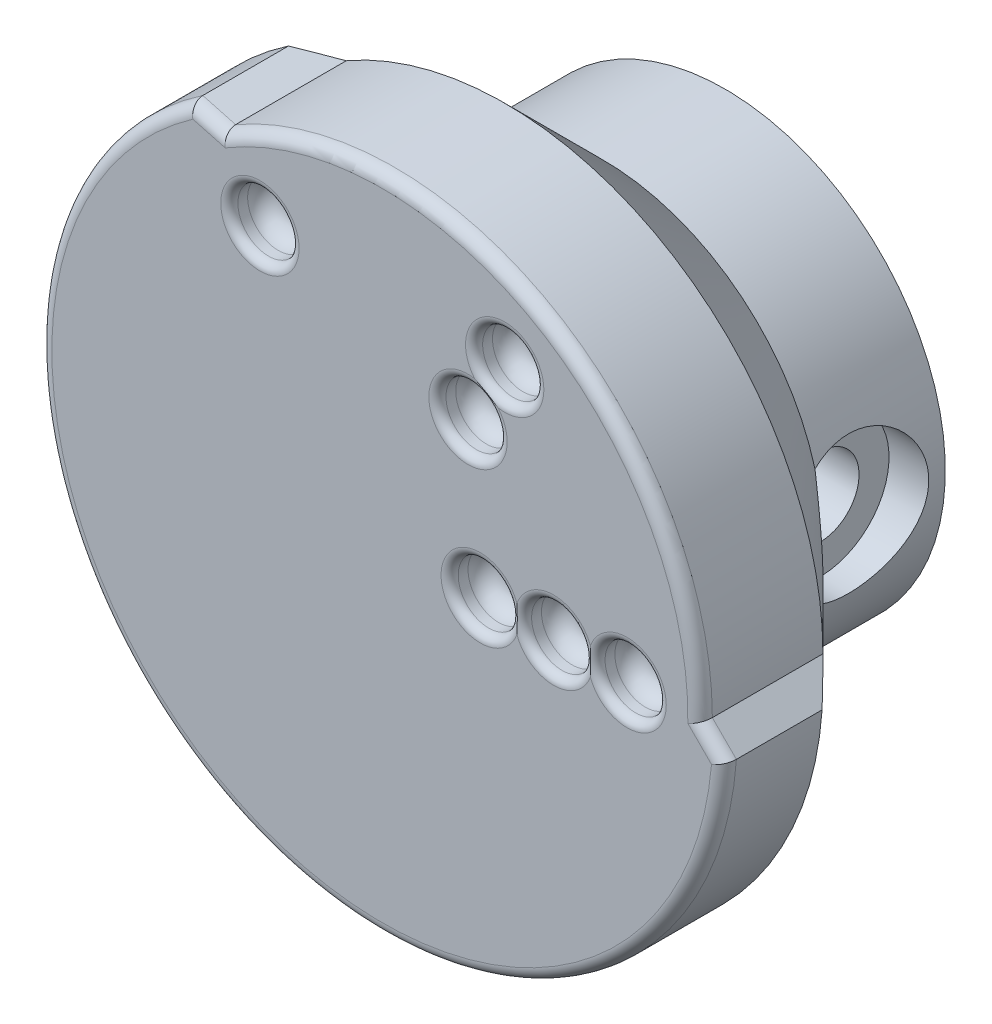
SolidWorks part; units mm, degrees
ref_plane "Front Plane" through (0, 0, 0) normal (0, 0, 1) x (1, 0, 0)
ref_plane "Top Plane" through (0, 0, 0) normal (0, 1, 0) x (1, 0, 0)
ref_plane "Right Plane" through (0, 0, 0) normal (1, 0, 0) x (0, 0, -1)
sketch "Sketch1" plane through (0, 0, 0) normal (0, 0, 1) x (1, 0, 0)
  circle A0 centre (0, 0) radius 32.5
  dimension "D1" = 65
extrude "Boss-Extrude1" add sketch "Sketch1" along normal blind 13.25
sketch "Sketch2" plane through (0, 0, 13.25) normal (0, 0, 1) x (1, 0, 0)
  circle A0 centre (0, 0) radius 25
  dimension "D1" = 50
extrude "Cut-Extrude1" cut sketch "Sketch2" against normal blind 9.25
sketch "Sketch3" plane through (0, 0, 4) normal (0, 0, 1) x (1, 0, 0)
  line L1 (0, 4.7631) -> (-4.125, 2.3816)
  line L2 (-4.125, 2.3816) -> (-4.125, -2.3816)
  line L3 (-4.125, -2.3816) -> (0, -4.7631)
  line L4 (0, -4.7631) -> (4.125, -2.3816)
  line L5 (4.125, -2.3816) -> (4.125, 2.3816)
  line L6 (4.125, 2.3816) -> (0, 4.7631)
  circle A0 centre (0, 0) radius 4.125 construction
  dimension "D1" = 8.25
extrude "Cut-Extrude2" cut sketch "Sketch3" against normal through all
fillet "Fillet1" [suppressed] radius 2
fillet "Inner Fillet" [suppressed] radius 2
sketch "Sketch4" plane through (0, 0, 13.25) normal (0, 0, 1) x (1, 0, 0)
  circle A0 centre (0, 0) radius 29.5
  dimension "D1" = 59
extrude "Cut-Extrude3" cut sketch "Sketch4" against normal blind 3
sketch "Sketch5" plane through (0, 0, 0) normal (0, 0, -1) x (-1, 0, 0)
  line L0 (0, 37.5748) -> (0, -64.9877) construction
sketch "Sketch6" plane through (0, 0, 0) normal (1, 0, 0) x (0, 0, -1)
  line L0 (-13.25, 32.5) -> (-13.25, -32.5) construction
  line L1 (0, -32.5) -> (0, 32.5) construction
  line L2 (-13.25, 32.5) -> (-13.25, -32.5) construction
  line L3 (0, -32.5) -> (0, 32.5) construction
sketch "Sketch7" plane through (0, 0, 0) normal (0, 0, -1) x (-1, 0, 0)
  line L0 (33.5665, -32.5) -> (-65.5928, -32.5) construction
  line L7 (-4.125, 2.3816) -> (-4.125, -2.3816)
  line L8 (0, 4.7631) -> (-4.125, 2.3816)
  line L9 (4.125, 2.3816) -> (0, 4.7631)
  line L10 (4.125, -2.3816) -> (4.125, 2.3816)
  line L11 (0, -4.7631) -> (4.125, -2.3816)
  line L12 (-4.125, -2.3816) -> (0, -4.7631)
  line L13 (-4.125, 2.3816) -> (-4.125, -2.3816)
  line L14 (0, 4.7631) -> (-4.125, 2.3816)
  line L15 (4.125, 2.3816) -> (0, 4.7631)
  line L16 (4.125, -2.3816) -> (4.125, 2.3816)
  line L17 (0, -4.7631) -> (4.125, -2.3816)
  line L18 (-4.125, -2.3816) -> (0, -4.7631)
  circle A0 centre (-23.4554, -36.9311) radius 4 construction
  circle A1 centre (-23.4554, -36.9311) radius 9
  arc A2 (-23.9766, -21.9402) -> (-9.6651, -31.0296) centre (-23.4554, -36.9311) ccw
  circle A3 centre (-23.4554, -36.9311) radius 11.25 construction
  circle A4 centre (0, 0) radius 32.5 construction
  circle A6 centre (0, 0) radius 32.5
  arc A7 (-9.6651, -31.0296) -> (-23.9766, -21.9402) centre (0, 0) ccw
  dimension "D1" = 8
  dimension "D2" = 18
  dimension "D3" = 30
  dimension "D4" = 22.5
  dimension "D5" = 0
  dimension "D6" = 0
extrude "Boss-Extrude2" add sketch "Sketch7" against normal blind 1.5
sketch "Sketch8" plane through (0, 0, 1.5) normal (0, 0, 1) x (1, 0, 0)
  line L0 (23.4554, -36.9311) -> (23.4554, -25.6811) construction
  line L1 (23.4554, -36.9311) -> (33.1982, -42.5561) construction
  line L2 (23.4554, -36.9311) -> (13.7126, -42.5561) construction
  arc A0 (33.3207, -42.3382) -> (23.7054, -25.6839) centre (23.4554, -36.9311) ccw
  arc A1 (9.6651, -31.0296) -> (23.9766, -21.9402) centre (23.4554, -36.9311) ccw construction
  circle A2 centre (23.4554, -36.9311) radius 15
  arc A3 (23.6707, -25.8082) -> (23.2401, -25.8082) centre (23.4554, -36.9311) ccw
  arc A4 (23.2054, -25.6839) -> (23.2401, -25.8082) centre (23.4554, -25.6811) ccw
  arc A5 (9.6651, -31.0296) -> (23.9766, -21.9402) centre (23.4554, -36.9311) ccw
  arc A6 (9.6651, -31.0296) -> (23.9766, -21.9402) centre (0, 0) ccw
  circle A7 centre (23.4554, -36.9311) radius 15
  arc A9 (23.6707, -25.8082) -> (23.7054, -25.6839) centre (23.4554, -25.6811) ccw
  arc A10 (33.3207, -42.3382) -> (33.1957, -42.3061) centre (33.1982, -42.5561) ccw
  arc A11 (32.9805, -42.679) -> (33.0708, -42.7712) centre (33.1982, -42.5561) ccw
  arc A12 (23.2054, -25.6839) -> (13.59, -42.3382) centre (23.4554, -36.9311) ccw
  arc A13 (13.84, -42.7712) -> (13.9303, -42.679) centre (13.7126, -42.5561) ccw
  arc A14 (13.84, -42.7712) -> (33.0708, -42.7712) centre (23.4554, -36.9311) ccw
  arc A15 (13.715, -42.3061) -> (13.59, -42.3382) centre (13.7126, -42.5561) ccw
  arc A16 (13.715, -42.3061) -> (13.9303, -42.679) centre (23.4554, -36.9311) ccw
  arc A17 (32.9805, -42.679) -> (33.1957, -42.3061) centre (23.4554, -36.9311) ccw
  dimension "D1" = 22.5
  dimension "D3" = 22.25
  dimension "D4" = 0.5
  dimension "D7" = 0.5
  dimension "D8" = 0.5
  dimension "D5" = 120
  dimension "D6" = 120
  dimension "D2" = 0
sketch "Sketch9" plane through (0, 0, 1.5) normal (0, 0, 1) x (1, 0, 0)
  circle A0 centre (23.4554, -36.9311) radius 11.125
  arc A1 (9.6651, -31.0296) -> (23.9766, -21.9402) centre (23.4554, -36.9311) ccw construction
  arc A2 (9.6651, -31.0296) -> (23.9766, -21.9402) centre (0, 0) ccw construction
  arc A3 (9.6651, -31.0296) -> (23.9766, -21.9402) centre (23.4554, -36.9311) ccw
  arc A4 (9.6651, -31.0296) -> (23.9766, -21.9402) centre (0, 0) ccw
  dimension "D1" = 22.25
extrude "Boss-Extrude5" add sketch "Sketch9" along normal blind 7.5
sketch "Sketch10" plane through (0, 0, 13.25) normal (0, 0, 1) x (1, 0, 0)
  line L0 (23.4554, -25.5561) -> (23.4554, -36.9311) construction
  line L1 (23.4554, -36.9311) -> (33.3064, -42.6186) construction
  line L2 (23.4554, -36.9311) -> (13.6043, -42.6186) construction
  circle A0 centre (23.4554, -36.9311) radius 11.125 construction
  arc A1 (13.6139, -42.1187) -> (14.0421, -42.8603) centre (23.4554, -36.9311) ccw
  arc A2 (13.8638, -43.046) -> (33.047, -43.046) centre (23.4554, -36.9311) ccw
  arc A3 (23.8835, -25.8144) -> (23.9553, -25.5671) centre (23.4554, -25.5561) ccw
  arc A4 (13.6139, -42.1187) -> (13.3639, -42.1802) centre (13.6043, -42.6186) ccw
  arc A5 (32.8687, -42.8603) -> (33.047, -43.046) centre (33.3064, -42.6186) ccw
  circle A6 centre (23.4554, -36.9311) radius 11.125 construction
  arc A7 (32.8687, -42.8603) -> (33.2968, -42.1187) centre (23.4554, -36.9311) ccw
  arc A8 (13.8638, -43.046) -> (14.0421, -42.8603) centre (13.6043, -42.6186) ccw
  circle A9 centre (23.4554, -36.9311) radius 11.375 construction
  arc A10 (33.5468, -42.1802) -> (33.2968, -42.1187) centre (33.3064, -42.6186) ccw
  arc A11 (33.5468, -42.1802) -> (23.9553, -25.5671) centre (23.4554, -36.9311) ccw
  arc A12 (23.8835, -25.8144) -> (23.0272, -25.8144) centre (23.4554, -36.9311) ccw
  arc A13 (22.9555, -25.5671) -> (23.0272, -25.8144) centre (23.4554, -25.5561) ccw
  arc A14 (22.9555, -25.5671) -> (13.3639, -42.1802) centre (23.4554, -36.9311) ccw
  dimension "D4" = 1
  dimension "D5" = 1
  dimension "D6" = 1
  dimension "D2" = 120
  dimension "D3" = 120
  dimension "D1" = 0.25
extrude "Cut-Extrude4" cut sketch "Sketch10" against normal up to surface (11.75 mm away) up to face at (34.5804, -36.9311, 1.5)
sketch "Sketch11" plane through (0, 0, 9) normal (0, 0, 1) x (1, 0, 0)
  circle A91 centre (23.4554, -36.9311) radius 11.9872
  arc A104 (22.8427, -25.7028) -> (18.685, -26.7481) centre (23.4554, -36.9311) ccw
  arc A105 (22.8427, -25.7028) -> (22.9615, -25.9472) centre (23.4554, -25.5561) ccw
  arc A106 (23.9493, -25.9472) -> (22.9615, -25.9472) centre (23.4554, -36.9311) ccw
  arc A107 (23.9493, -25.9472) -> (24.0681, -25.7028) centre (23.4554, -25.5561) ccw
  arc A108 (33.4857, -42.0147) -> (24.0681, -25.7028) centre (23.4554, -36.9311) ccw
  arc A109 (33.4857, -42.0147) -> (33.2147, -41.9953) centre (33.3064, -42.6186) ccw
  arc A110 (32.7208, -42.8508) -> (33.2147, -41.9953) centre (23.4554, -36.9311) ccw
  arc A111 (32.7208, -42.8508) -> (32.873, -43.0759) centre (33.3064, -42.6186) ccw
  arc A112 (13.6961, -41.9953) -> (13.425, -42.0147) centre (13.6043, -42.6186) ccw
  arc A113 (16.2665, -28.2841) -> (13.425, -42.0147) centre (23.4554, -36.9311) ccw
  arc A114 (14.0377, -43.0759) -> (32.873, -43.0759) centre (23.4554, -36.9311) ccw
  arc A115 (14.0377, -43.0759) -> (14.19, -42.8508) centre (13.6043, -42.6186) ccw
  arc A116 (13.6961, -41.9953) -> (14.19, -42.8508) centre (23.4554, -36.9311) ccw
  arc A117 (22.8427, -25.7028) -> (16.2665, -28.2841) centre (23.4554, -36.9311) ccw
  arc A118 (22.8427, -25.7028) -> (22.9615, -25.9472) centre (23.4554, -25.5561) ccw
  arc A119 (23.9493, -25.9472) -> (22.9615, -25.9472) centre (23.4554, -36.9311) ccw
  arc A120 (23.9493, -25.9472) -> (24.0681, -25.7028) centre (23.4554, -25.5561) ccw
  arc A121 (33.4857, -42.0147) -> (24.0681, -25.7028) centre (23.4554, -36.9311) ccw
  arc A122 (33.4857, -42.0147) -> (33.2147, -41.9953) centre (33.3064, -42.6186) ccw
  arc A123 (32.7208, -42.8508) -> (33.2147, -41.9953) centre (23.4554, -36.9311) ccw
  arc A124 (32.7208, -42.8508) -> (32.873, -43.0759) centre (33.3064, -42.6186) ccw
  arc A125 (13.6961, -41.9953) -> (13.425, -42.0147) centre (13.6043, -42.6186) ccw
  arc A126 (16.2665, -28.2841) -> (13.425, -42.0147) centre (23.4554, -36.9311) ccw
  arc A127 (14.0377, -43.0759) -> (32.873, -43.0759) centre (23.4554, -36.9311) ccw
  arc A128 (14.0377, -43.0759) -> (14.19, -42.8508) centre (13.6043, -42.6186) ccw
  arc A129 (13.6961, -41.9953) -> (14.19, -42.8508) centre (23.4554, -36.9311) ccw
  dimension "D1" = 0.13
extrude "Boss-Extrude6" add sketch "Sketch11" against normal up to surface (7.5 mm away) up to face at (23.4554, -36.9311, 1.5)
sketch "Sketch12" plane through (0, 0, 9) normal (0, 0, 1) x (1, 0, 0)
  arc A0 (18.6299, -26.6304) -> (16.1834, -28.1842) centre (0, 0) ccw construction
  arc A1 (18.6299, -26.6304) -> (16.1834, -28.1842) centre (23.4554, -36.9311) ccw construction
  arc A2 (16.1834, -28.1842) -> (18.6299, -26.6304) centre (0, 0) ccw
  arc A3 (18.6299, -26.6304) -> (16.1834, -28.1842) centre (23.4554, -36.9311) ccw
extrude "Boss-Extrude7" add sketch "Sketch12" along normal up to surface (4.25 mm away) up to face at (-0.0335, 0.0528, 13.25)
chamfer "Chamfer1" distance 1 angle 45 9 edges at (14.4554, -36.9311, 0) (-2.0625, -3.5724, 0) (2.0625, -3.5724, 0) (4.125, 0, 0) (2.0625, 3.5724, 0) (-4.125, 0, 0) (-2.0625, 3.5724, 0) (31.4972, -49.5932, 0) (-17.424, 27.4345, 0)
sketch "Sketch13" plane through (0, 0, 0) normal (0, 0, -1) x (-1, 0, 0)
  line L0 (0, 15) -> (0, -15) construction
  line L1 (-1, 15) -> (-1, 1.7321)
  line L2 (1, 15) -> (1, 1.7321)
  line L3 (-1, 15) -> (1, 15)
  line L4 (1, -15) -> (-1, -15)
  line L5 (13.4904, -6.634) -> (2, 0)
  line L6 (13.4904, -6.634) -> (12.4904, -8.366)
  line L7 (12.4904, -8.366) -> (1, -1.7321)
  line L8 (-13.4904, 6.634) -> (-12.4904, 8.366)
  line L9 (-12.4904, -8.366) -> (-1, -1.7321)
  line L10 (-12.4904, -8.366) -> (-13.4904, -6.634)
  line L11 (-13.4904, -6.634) -> (-2, 0)
  line L12 (12.4904, 8.366) -> (13.4904, 6.634)
  line L13 (1, 1.7321) -> (12.4904, 8.366)
  line L15 (1, 15) -> (1, -15) construction
  line L17 (2, 0) -> (13.4904, 6.634)
  line L18 (1, -1.7321) -> (1, -15)
  line L21 (-1, -1.7321) -> (-1, -15)
  line L22 (-1, 15) -> (-1, -15) construction
  line L23 (-2, 0) -> (-13.4904, 6.634)
  line L26 (-1, 1.7321) -> (-12.4904, 8.366)
  circle A0 centre (0, 0) radius 10.4359 construction
  circle A1 centre (0, 0) radius 10.4359 construction
  circle A2 centre (0, 0) radius 10.4359 construction
  point P24 (0, 0)
  dimension "D1" = 30
  dimension "D2" = 1
  dimension "D3" = 1
  dimension "D4" = 3
extrude "Cut-Extrude5" cut sketch "Sketch13" against normal blind 2
chamfer "Chamfer2" distance 1 angle 45 36 edges at (-9.3077, 4.2191, 0) (-12.9904, 7.5, 0) (-8.3077, 5.9511, 0) (-7.8077, 5.6625, 2) (-12.9904, 7.5, 2) (-8.8077, 3.9304, 2) (-8.3077, -5.9511, 0) (-12.9904, -7.5, 0) (-9.3077, -4.2191, 0) (-7.8077, -5.6625, 2) (-12.9904, -7.5, 2) (-8.8077, -3.9304, 2) (1, -9.5929, 2) (0, -15, 2) (-1, -9.5929, 2) (1, -10.1702, 0) (0, -15, 0) (-1, -10.1702, 0) (8.3077, -5.9511, 0) (12.9904, -7.5, 0) (9.3077, -4.2191, 0) (7.8077, -5.6625, 2) (12.9904, -7.5, 2) (8.8077, -3.9304, 2) (8.8077, 3.9304, 2) (12.9904, 7.5, 2) (7.8077, 5.6625, 2) (9.3077, 4.2191, 0) (12.9904, 7.5, 0) (8.3077, 5.9511, 0) (1, 10.1702, 0) (-1, 10.1702, 0) (0, 15, 0) (1, 9.5929, 2) (-1, 9.5929, 2) (0, 15, 2)
sketch "Sketch14" plane through (0, 0, 0) normal (0, 0, -1) x (-1, 0, 0)
  line L0 (0, 0) -> (0, 16.25) construction
  line L1 (0, 0) -> (14.0729, -8.125) construction
  line L3 (-14.0729, -8.125) -> (0, 0) construction
  circle A0 centre (0, 0) radius 16.25
  dimension "D1" = 32.5
  dimension "D2" = 120
  dimension "D3" = 120
sketch "Sketch15" plane through (0, 0, 13.25) normal (0, 0, 1) x (1, 0, 0)
  line L6 (4.125, 2.3816) -> (0, 4.7631)
  line L7 (4.125, -2.3816) -> (4.125, 2.3816)
  line L8 (0, -4.7631) -> (4.125, -2.3816)
  line L9 (-4.125, -2.3816) -> (0, -4.7631)
  line L10 (-4.125, 2.3816) -> (-4.125, -2.3816)
  line L11 (0, 4.7631) -> (-4.125, 2.3816)
  line L12 (4.125, 2.3816) -> (0, 4.7631)
  line L13 (4.125, -2.3816) -> (4.125, 2.3816)
  line L14 (0, -4.7631) -> (4.125, -2.3816)
  line L15 (-4.125, -2.3816) -> (0, -4.7631)
  line L16 (-4.125, 2.3816) -> (-4.125, -2.3816)
  line L17 (0, 4.7631) -> (-4.125, 2.3816)
  circle A0 centre (0, 0) radius 9
  dimension "D2" = 18
  dimension "D1" = 0
extrude "Boss-Extrude9" add sketch "Sketch15" along normal blind 13 separate body
sketch "Sketch16" plane through (0, 0, 26.25) normal (0, 0, 1) x (1, 0, 0)
  circle A0 centre (0, 0) radius 14
  dimension "D1" = 28
extrude "Boss-Extrude10" add sketch "Sketch16" along normal blind 10
sketch "Sketch17" plane through (0, 0, 0) normal (0, 0, -1) x (-1, 0, 0)
  line L1 (-91.0279, 41.9057) -> (60.7321, 41.9057)
  line L2 (-91.0279, 41.9057) -> (-91.0279, -58.8865)
  line L3 (-91.0279, -58.8865) -> (60.7321, -58.8865)
  line L4 (60.7321, 41.9057) -> (60.7321, -58.8865)
extrude "Cut-Extrude6" cut sketch "Sketch17" against normal up to surface (13.25 mm away) up to face at (9, 0, 13.25)
fillet "Fillet2" [suppressed] radius 5
chamfer "Chamfer3" distance 5 angle 45 1 edges at (9, 0, 26.25)
sketch "Sketch18" plane through (4.125, 0, 0) normal (-1, 0, 0) x (0, 0, 1)
  line L0 (26.25, 14) -> (26.25, -14) construction
  circle A0 centre (19.75, 0) radius 1.6
  dimension "D1" = 3.2
  dimension "D2" = 6.5
extrude "Cut-Extrude7" cut sketch "Sketch18" against normal through all both and the other way through all
sketch "Sketch19" plane through (4.125, 0, 0) normal (-1, 0, 0) x (0, 0, 1)
  circle A0 centre (19.75, 0) radius 2.825
  dimension "D1" = 5.65
extrude "Cut-Extrude8" cut sketch "Sketch19" along direction (-1, 0, 0) on the side against the normal offset from surface (6.75 mm away) 10 from offset 3.25 up to face at (4.125, 0, 21.35) offset against normal yes
sketch "Sketch20" plane through (-4.125, 0, 0) normal (1, 0, 0) x (0, 0, -1)
  line L1 (-16.488, 0) -> (-18.119, 2.825)
  line L2 (-18.119, 2.825) -> (-21.381, 2.825)
  line L3 (-21.381, 2.825) -> (-23.012, 0)
  line L4 (-23.012, 0) -> (-21.381, -2.825)
  line L5 (-21.381, -2.825) -> (-18.119, -2.825)
  line L6 (-18.119, -2.825) -> (-16.488, 0)
  circle A0 centre (-19.75, 0) radius 2.825 construction
  dimension "D1" = 5.65
extrude "Cut-Extrude9" cut sketch "Sketch20" against normal blind 10 from offset 2.75 offset against normal yes
sketch "Sketch21" plane through (0, 0, 36.25) normal (0, 0, 1) x (1, 0, 0)
  line L0 (-14.3337, -5) -> (16.6286, -5) construction
  line L1 (0, 0) -> (0, -5) construction
  text T0 "<b>PULL</b>" font "Century Gothic" height 8
  dimension "D1" = 5
extrude "Cut-Extrude10" [suppressed] cut sketch "Sketch21" against normal blind 5
sketch "Sketch22" plane through (0, 0, 13.25) normal (0, 0, -1) x (-1, 0, 0)
  line L0 (6.25, 10.8253) -> (-6.25, -10.8253) construction
  dimension "D1" = 25
sketch "Sketch23" plane through (0, 0, 13.25) normal (0, 0, -1) x (-1, 0, 0)
  circle A1 centre (0, 0) radius 9
  circle A2 centre (0, 0) radius 9
  dimension "D1" = 0
extrude "Cut-Extrude11" cut sketch "Sketch23" against normal blind 3
sketch "Sketch24" plane through (-6.875, 0, 0) normal (-1, 0, 0) x (0, 0, 1)
  line L6 (16.488, 0) -> (18.119, -2.825)
  line L7 (18.119, -2.825) -> (21.381, -2.825)
  line L8 (21.381, -2.825) -> (23.012, 0)
  line L9 (23.012, 0) -> (21.381, 2.825)
  line L10 (21.381, 2.825) -> (18.119, 2.825)
  line L11 (18.119, 2.825) -> (16.488, 0)
  line L12 (16.488, 0) -> (18.119, -2.825)
  line L13 (18.119, -2.825) -> (21.381, -2.825)
  line L14 (21.381, -2.825) -> (23.012, 0)
  line L15 (23.012, 0) -> (21.381, 2.825)
  line L16 (21.381, 2.825) -> (18.119, 2.825)
  line L17 (18.119, 2.825) -> (16.488, 0)
  dimension "D1" = 0
extrude "Cut-Extrude12" cut sketch "Sketch24" against normal blind 0.5
sketch "Sketch25" plane through (0, 0, 36.25) normal (0, 0, 1) x (1, 0, 0)
  line L0 (-4.125, 2.3816) -> (0, 4.7631)
  line L1 (0, 4.7631) -> (-3.3607, 10.584)
  line L2 (-3.3607, 10.584) -> (-6.614, 11.4557)
  line L3 (-6.614, 11.4557) -> (-7.4857, 8.2024)
  line L4 (-7.4857, 8.2024) -> (-4.125, 2.3816)
  line L5 (-3.3607, 10.584) -> (-7.4857, 8.2024) construction
  circle A1 centre (0, 0) radius 14
  circle A2 centre (0, 0) radius 14
  dimension "D2" = 135
  dimension "D3" = 2.3816
  dimension "D4" = 6.7214
  dimension "D1" = 0
extrude "Cut-Extrude13" cut sketch "Sketch25" against normal blind 6
sketch "Sketch26" plane through (0, 0, 36.25) normal (0, 0, 1) x (1, 0, 0)
  line L5 (-6.614, 11.4557) -> (-7.4857, 8.2024)
  line L6 (-7.4857, 8.2024) -> (-4.125, 2.3816)
  line L7 (-4.125, 2.3816) -> (0, 4.7631)
  line L8 (0, 4.7631) -> (-3.3607, 10.584)
  line L9 (-3.3607, 10.584) -> (-6.614, 11.4557)
  line L10 (-6.614, 11.4557) -> (-7.4857, 8.2024)
  line L11 (-7.4857, 8.2024) -> (-4.125, 2.3816)
  line L12 (-4.125, 2.3816) -> (0, 4.7631)
  line L13 (0, 4.7631) -> (-3.3607, 10.584)
  line L14 (-3.3607, 10.584) -> (-6.614, 11.4557)
  dimension "D1" = 0
extrude "Cut-Extrude14" cut sketch "Sketch26" against normal blind 4
sketch "Sketch27" plane through (0, 0, 26.25) normal (0, 0, -1) x (-1, 0, 0)
  line L6 (4.125, 2.3816) -> (0, 4.7631)
  line L7 (0, 4.7631) -> (-4.125, 2.3816)
  line L8 (-4.125, 2.3816) -> (-4.125, -2.3816)
  line L9 (-4.125, -2.3816) -> (0, -4.7631)
  line L10 (0, -4.7631) -> (4.125, -2.3816)
  line L11 (4.125, -2.3816) -> (4.125, 2.3816)
  line L12 (4.125, 2.3816) -> (0, 4.7631)
  line L13 (0, 4.7631) -> (-4.125, 2.3816)
  line L14 (-4.125, 2.3816) -> (-4.125, -2.3816)
  line L15 (-4.125, -2.3816) -> (0, -4.7631)
  line L16 (0, -4.7631) -> (4.125, -2.3816)
  line L17 (4.125, -2.3816) -> (4.125, 2.3816)
  dimension "D1" = 0
extrude "Cut-Extrude15" cut sketch "Sketch27" against normal blind 2
chamfer "Chamfer4" distance 2 angle 45 6 edges at (-2.0625, -3.5724, 28.25) (2.0625, -3.5724, 28.25) (4.125, 0, 28.25) (2.0625, 3.5724, 28.25) (-2.0625, 3.5724, 28.25) (-4.125, 0, 28.25)
sketch "Sketch28" plane through (0, 0, 32.25) normal (0, 0, 1) x (1, 0, 0)
  line L5 (-3.3607, 10.584) -> (-6.614, 11.4557)
  line L6 (-6.614, 11.4557) -> (-7.4857, 8.2024)
  line L7 (-7.4857, 8.2024) -> (-4.125, 2.3816)
  line L8 (-4.125, 2.3816) -> (0, 4.7631)
  line L9 (0, 4.7631) -> (-3.3607, 10.584)
  line L10 (-3.3607, 10.584) -> (-6.614, 11.4557)
  line L11 (-6.614, 11.4557) -> (-7.4857, 8.2024)
  line L12 (-7.4857, 8.2024) -> (-4.125, 2.3816)
  line L13 (-4.125, 2.3816) -> (0, 4.7631)
  line L14 (0, 4.7631) -> (-3.3607, 10.584)
  dimension "D1" = 0
extrude "Cut-Extrude16" cut sketch "Sketch28" against normal up to surface (2 mm away) up to face at (-4.3171, 7.4774, 30.25)
sketch "Sketch29" plane through (0, 0, 30.25) normal (0, 0, 1) x (1, 0, 0)
  line L0 (-7, 12.1244) -> (-2.0625, 3.5724) construction
  line L1 (0, 4.7631) -> (-4.125, 2.3816) construction
  line L2 (-6.131, 12.5862) -> (-6.4913, 11.2433)
  line L3 (-6.4913, 11.2433) -> (-7.8333, 11.6034)
  line L4 (-7.8333, 11.6034) -> (-8.7579, 13.2049)
  line L5 (-8.7579, 13.2049) -> (-7.0556, 14.1877)
  line L6 (-7.0556, 14.1877) -> (-6.131, 12.5862)
  line L7 (6.1323, 12.5855) -> (7.0568, 14.187)
  line L8 (7.0568, 14.187) -> (8.7591, 13.2042)
  line L9 (8.7591, 13.2042) -> (7.8344, 11.6027)
  line L10 (7.8344, 11.6027) -> (6.4913, 11.2433)
  line L11 (6.4913, 11.2433) -> (6.1323, 12.5855)
  line L12 (13.9655, 0.9821) -> (15.8147, 0.9821)
  line L13 (15.8147, 0.9821) -> (15.8147, -0.9835)
  line L14 (15.8147, -0.9835) -> (13.9654, -0.9835)
  line L15 (13.9654, -0.9835) -> (12.9827, 0)
  line L16 (12.9827, 0) -> (13.9655, 0.9821)
  line L17 (0, 0) -> (-6.4913, 11.2433) construction
  line L18 (0, 0) -> (6.4913, 11.2433) construction
  circle A0 centre (0, 0) radius 14 construction
  dimension "D2" = 60
  dimension "D1" = 3
extrude "Cut-Extrude17" cut sketch "Sketch29" against normal through all
sketch "Sketch30" plane through (0, 0, 30.25) normal (0, 0, 1) x (1, 0, 0)
  line L0 (-7.8333, 11.6034) -> (-6.4913, 11.2433) construction
  line L1 (12.9827, 0) -> (13.9654, -0.9835) construction
  line L2 (-7.8333, 11.6034) -> (-6.4913, 11.2433)
  line L3 (12.9827, 0) -> (13.9654, -0.9835)
  arc A0 (12.9827, 0) -> (-6.4913, 11.2433) centre (0, 0) ccw
  arc A1 (13.9654, -0.9835) -> (-7.8333, 11.6034) centre (0, 0) ccw
extrude "Cut-Extrude18" cut sketch "Sketch30" against normal blind 10
sketch "Sketch31" plane through (0, 0, 30.25) normal (0, 0, 1) x (1, 0, 0)
  line L0 (0, 0) -> (-6.4913, 11.2433) construction
  line L1 (0, 0) -> (12.9827, 0) construction
  line L2 (8.0869, 14.0068) -> (-6.4913, -11.2433) construction
  circle A0 centre (3.5, 6.0622) radius 1.25
  circle A1 centre (-5, 8.6603) radius 1.25
  circle A2 centre (7, 0) radius 1.25
  circle A3 centre (4, 0) radius 1.25
  circle A4 centre (5, 8.6603) radius 1.25
  circle A5 centre (10, 0) radius 1.25
  point P9 (0, 0)
  dimension "D2" = 2.5
  dimension "D3" = 2.5
  dimension "D4" = 2.5
  dimension "D5" = 10
  dimension "D6" = 10
  dimension "D7" = 10
  dimension "D8" = 2.5
  dimension "D9" = 2.5
  dimension "D10" = 2.5
  dimension "D11" = 3
  dimension "D12" = 3
  dimension "D13" = 3
  dimension "D1" = 3
extrude "Cut-Extrude19" cut sketch "Sketch31" against normal blind 1.5
fillet "Fillet3" radius 0.5 4 edges at (13.474, -0.4918, 30.25) (-7.1623, 11.4234, 30.25) (6.4913, 11.2433, 30.25) (-7.0006, -12.124, 30.25)
sketch "Sketch32" plane through (0, 0, 30.25) normal (0, 0, 1) x (1, 0, 0)
  line L0 (0, 0) -> (10, 0) construction
  line L1 (5, 8.6603) -> (0, 0) construction
  line L2 (0, 0) -> (-5, 8.6603) construction
sketch "Sketch33" plane through (0, 0, 30.25) normal (0, 0, 1) x (1, 0, 0)
  circle A0 centre (-5, 8.6603) radius 1.25 construction
  circle A1 centre (5, 8.6603) radius 1.25 construction
  circle A2 centre (10, 0) radius 1.25 construction
  circle A3 centre (-5, 8.6603) radius 1.25
  circle A4 centre (5, 8.6603) radius 1.25
  circle A5 centre (10, 0) radius 1.25
fillet "Fillet6" radius 0.35 6 edges at (11.25, 0, 30.25) (6.25, 8.6603, 30.25) (4.75, 6.0622, 30.25) (8.25, 0, 30.25) (5.25, 0, 30.25) (-3.75, 8.6603, 30.25)
fillet "Fillet7" radius 0.75 6 edges at (5.25, 0, 28.75) (8.25, 0, 28.75) (4.75, 6.0622, 28.75) (6.25, 8.6603, 28.75) (11.25, 0, 28.75) (-3.75, 8.6603, 28.75)
